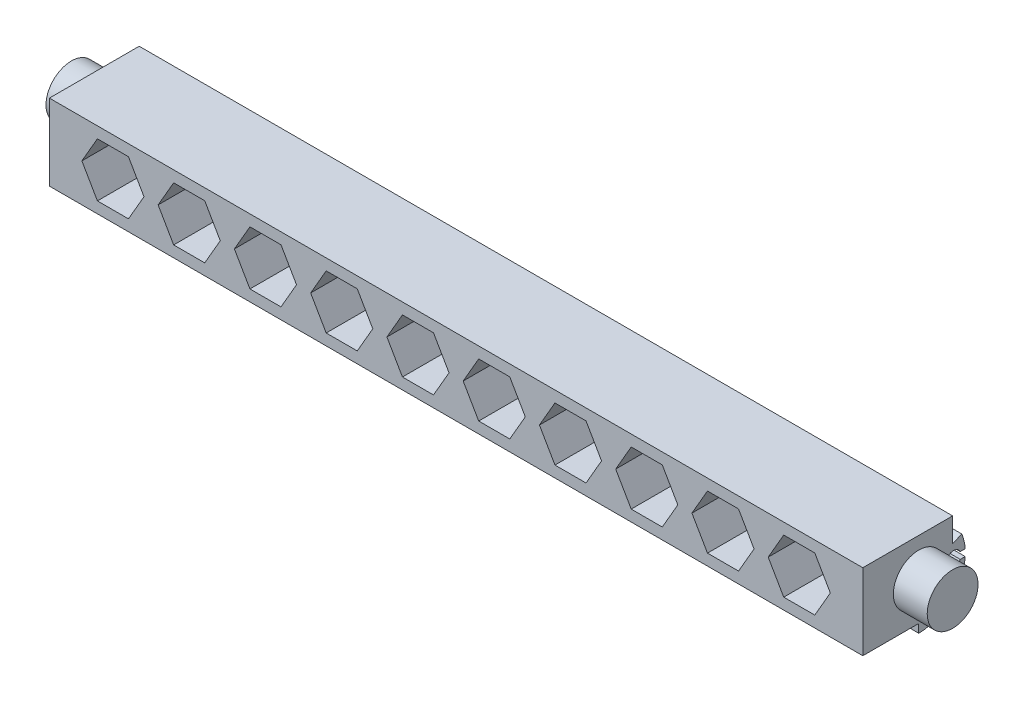
SolidWorks part; units mm, degrees
ref_plane "Front Plane" through (0, 0, 0) normal (0, 0, 1) x (1, 0, 0)
ref_plane "Top Plane" through (0, 0, 0) normal (0, 1, 0) x (1, 0, 0)
ref_plane "Right Plane" through (0, 0, 0) normal (1, 0, 0) x (0, 0, -1)
sketch "Sketch1" plane through (0, 0, 0) normal (0, 0, 1) x (1, 0, 0)
  line L1 (-4.5, -4.5) -> (4.5, -4.5)
  line L2 (-4.5, -4.5) -> (-4.5, 4.5)
  line L3 (-4.5, 4.5) -> (4.5, 4.5)
  line L4 (4.5, -4.5) -> (4.5, 4.5)
  line L5 (-4.5, -4.5) -> (4.5, 4.5) construction
  line L6 (-4.5, 4.5) -> (4.5, -4.5) construction
  line L7 (3.6662, 0) -> (1.8331, 3.175)
  line L8 (1.8331, 3.175) -> (-1.8331, 3.175)
  line L9 (-1.8331, 3.175) -> (-3.6662, 0)
  line L10 (-3.6662, 0) -> (-1.8331, -3.175)
  line L11 (-1.8331, -3.175) -> (1.8331, -3.175)
  line L12 (1.8331, -3.175) -> (3.6662, 0)
  circle A0 centre (0, 0) radius 3.175 construction
  circle A1 centre (0, 0) radius 3.175
  point P0 (0, 0)
  dimension "D1" = 6.35
  dimension "D2" = 9
  dimension "D3" = 9
extrude "Boss-Extrude1" add sketch "Sketch1" along normal blind 1.6 contours L1 L4 L3 L2 L12 L11 L10 L9 L8 L7 | A1 L7 L8 | A1 L8 L9 | A1 L9 L10 | A1 L12 L7 | A1 L11 L12 | A1 L10 L11 region at (-4.3727, 0, 0) region at (3.2816, 0, 0) region at (1.6408, 2.8419, 0) region at (1.6408, -2.8419, 0) region at (-1.6408, 2.8419, 0) region at (-1.6408, -2.8419, 0) region at (-3.2816, 0, 0)
extrude "Boss-Extrude2" add sketch "Sketch1<3>" along normal blind 0.5 from surface contours A1 L7 L8 | A1 | L1 L4 L3 L2 L12 L11 L10 L9 L8 L7 | A1 L12 L7 | A1 L11 L12 | A1 L10 L11 | A1 L9 L10 | A1 L8 L9 region at (-4.3727, 0, 0) region at (3.2816, 0, 0) region at (1.6408, 2.8419, 0) region at (0, 0, 0) region at (1.6408, -2.8419, 0) region at (-1.6408, 2.8419, 0) region at (-1.6408, -2.8419, 0) region at (-3.2816, 0, 0) starting at face at (3.175, 0, 1.6)
sketch "Sketch1<3>" plane through (0, 0, 0) normal (0, 0, 1) x (1, 0, 0) same geometry as "Sketch1"
extrude "Boss-Extrude3" add sketch "Sketch1<4>" along normal blind 8.5 from surface contours L1 L4 L3 L2 L12 L11 L10 L9 L8 L7 region at (-4.3727, 0, 0) starting at face at (0, 0, 2.1)
sketch "Sketch1<4>" plane through (0, 0, 0) normal (0, 0, 1) x (1, 0, 0) same geometry as "Sketch1"
pattern_linear "LPattern12" count 10 spacing 9 along (1, 0, 0) of "Boss-Extrude1", "Boss-Extrude2", "Boss-Extrude3"
ref_plane "Plane1" through (40.5, 0, 0) normal (-1, 0, 0) x (0, 0, 1)
sketch "Sketch2" plane through (-4.5, 0, 0) normal (-1, 0, 0) x (0, 0, 1)
  line L0 (0, -4.5) -> (0, 4.5) construction
  line L1 (4, 0) -> (-1.5, 0) construction
  line L2 (4, 0) -> (-1.0813, 2.1048)
  line L3 (4, 0) -> (4, -5.5) construction
  line L4 (4, 0) -> (6.1048, -5.0813)
  line L5 (0, -4.5) -> (0.346, -4.1108) construction
  line L6 (0.346, -4.1108) -> (2.3841, -5.9224) construction
  circle A0 centre (4, 0) radius 3
  arc A1 (-1.0813, 2.1048) -> (6.1048, -5.0813) centre (4, 0) ccw
  point P4 (0, 0)
  line M7 (0, 4.5) -> (0, -4.5)
  line M8 (0, -4.5) -> (10.6, -4.5)
  line M9 (10.6, -4.5) -> (10.6, 4.5)
  line M10 (10.6, 4.5) -> (0, 4.5)
  dimension "D1" = 6
  dimension "D5" = 5.5
  dimension "D2" = 4
  dimension "D3" = 22.5
  dimension "D4" = 22.5
extrude "Boss-Extrude4" add sketch "Sketch2" along normal blind 3 contours A0 L4 L2 M8 M9 M10 M7 | L4 A0 L2 | L2 A0 L4 | A0 L2 L4 M7 M8 | L2 A1 M7 | A1 L4 M8 region at (-4.5, -1.109, 2.891) region at (-4.5, 0.6654, 4.6654) region at (-4.5, -2.6184, 1.9882) region at (-4.5, 0.7563, 6.9584) region at (-4.5, -0.4961, -0.6517) region at (-4.5, -4.9243, 3.7516)
extrude "Boss-Extrude5" add sketch "Sketch2<3>" along normal blind 7 contours A0
sketch "Sketch2<3>" plane through (-4.5, 0, 0) normal (-1, 0, 0) x (0, 0, 1) same geometry as "Sketch2"
extrude "Boss-Extrude6" add sketch "Sketch2<4>" against normal blind 1 contours A1 L4 M8 | L2 A1 M7 region at (-4.5, -0.4961, -0.6517) region at (-4.5, -4.9243, 3.7516)
sketch "Sketch2<4>" plane through (-4.5, 0, 0) normal (-1, 0, 0) x (0, 0, 1) same geometry as "Sketch2"
extrude "Cut-Extrude3" cut sketch "Sketch2<5>" against normal blind 1 contours A1 M7 M8 region at (-4.5, -4.2665, 0.2696)
sketch "Sketch2<5>" plane through (-4.5, 0, 0) normal (-1, 0, 0) x (0, 0, 1) same geometry as "Sketch2"
mirror "Mirror1" about plane through (40.5, 0, 0) normal (-1, 0, 0) of "Cut-Extrude3", "Boss-Extrude5", "Boss-Extrude6", "Boss-Extrude4"
sketch "Sketch4" plane through (-7.5, 0, 0) normal (-1, 0, 0) x (0, 0, 1)
  line L0 (3.6, -4.9) -> (3.6, -5.4854)
  line L1 (4.4, -4.9) -> (4.4, -5.4854)
  line L2 (3.6, -4.9) -> (4.4, -4.9) construction
  line L3 (0, 1.6569) -> (0, 0)
  line L4 (0, 0) -> (-1.5, 0)
  line L5 (0, 1.6569) -> (-1.0813, 2.1048)
  line L6 (0, 1.6569) -> (-1.0813, 2.1048) construction
  arc A0 (4.4, -4.9) -> (3.6, -4.9) centre (4, -4.0938) ccw
  arc A1 (-1.0813, 2.1048) -> (6.1048, -5.0813) centre (4, 0) ccw construction
  arc A2 (3.6, -5.4854) -> (4.4, -5.4854) centre (4, 0) ccw
  arc A4 (-1.0813, 2.1048) -> (-1.5, 0) centre (4, 0) ccw
  point P17 (4, -5.5)
  line M7 (0, 1.6569) -> (-1.0813, 2.1048)
  arc M8 (-1.0813, 2.1048) -> (6.1048, -5.0813) centre (4, 0) ccw
  dimension "D1" = 1.8
  dimension "D2" = 0.6
  dimension "D3" = 0.8
extrude "Cut-Extrude1" cut sketch "Sketch4" against normal blind 4 contours A0 L2 | L2 L0 L1 M8 | L4 L3 M7 M8 region at (-7.5, -5.1976, 4) region at (-7.5, -4.0767, 4) region at (-7.5, 0.9107, -0.7171)
sketch "Sketch7" plane through (88.5, 0, 0) normal (1, 0, 0) x (0, 0, -1)
  line L0 (0.9, 0.4) -> (1.4854, 0.4)
  line L1 (0.9, 0.4) -> (0.9, -0.4) construction
  line L2 (1.4854, -0.4) -> (0.9, -0.4)
  line L3 (-5.864, -4.5) -> (-4, -4.5)
  line L4 (-4, -4.5) -> (-4, -5.5)
  line L5 (-5.864, -4.5) -> (-6.1048, -5.0813)
  arc A0 (0.9, 0.4) -> (0.9, -0.4) centre (0.0938, 0) ccw
  arc A1 (-6.1048, -5.0813) -> (1.0813, 2.1048) centre (-4, 0) ccw construction
  arc A2 (1.4854, 0.4) -> (1.4854, -0.4) centre (-4, 0) cw
  arc A3 (-4, -5.5) -> (-6.1048, -5.0813) centre (-4, 0) cw
  line M11 (-5.864, -4.5) -> (-6.1048, -5.0813)
  arc M12 (-6.1048, -5.0813) -> (1.0813, 2.1048) centre (-4, 0) ccw
  dimension "D1" = 1.8
  dimension "D2" = 0.6
  dimension "D3" = 0.8
extrude "Cut-Extrude2" cut sketch "Sketch7" against normal blind 4 contours L0 L1 L2 M12 | L1 A0 | L4 L3 M11 M12 region at (88.5, -4.9501, 4.9256) region at (88.5, 0, -1.1976) region at (88.5, 0, -0.0767)
